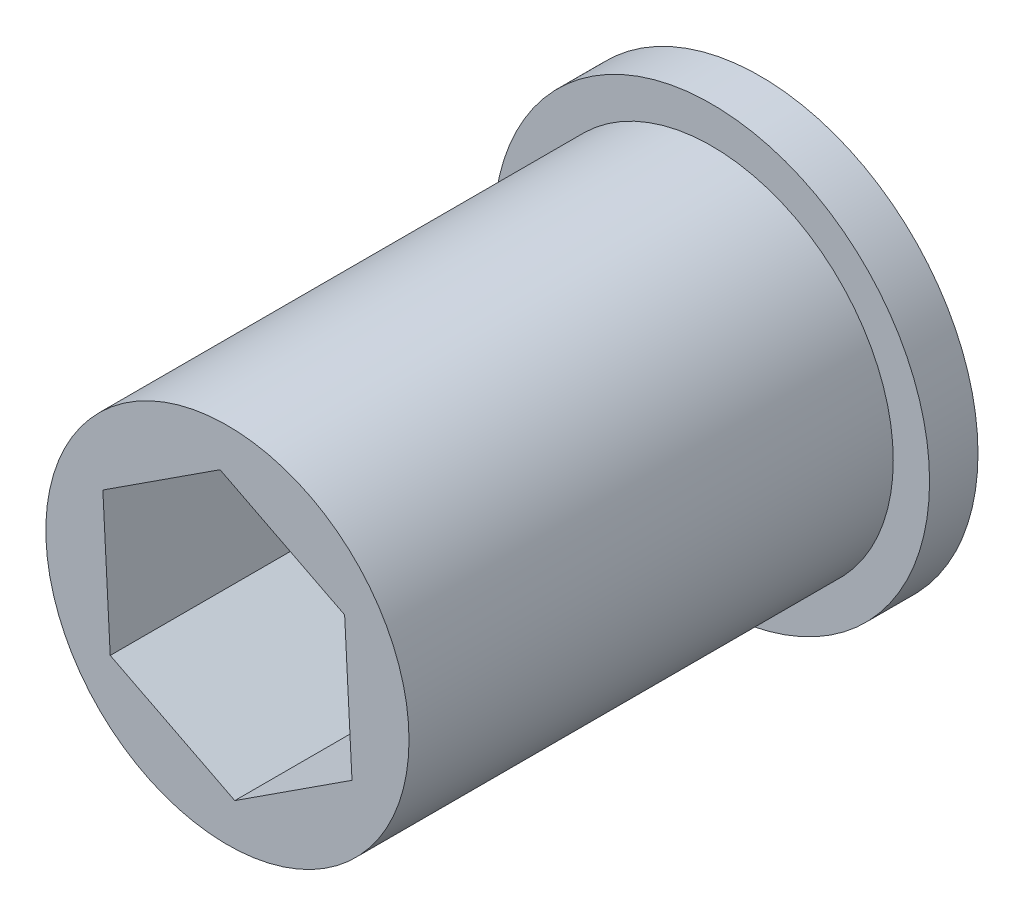
SolidWorks part; units mm, degrees
ref_plane "Front Plane" through (0, 0, 0) normal (0, 0, 1) x (1, 0, 0)
ref_plane "Top Plane" through (0, 0, 0) normal (0, 1, 0) x (1, 0, 0)
ref_plane "Right Plane" through (0, 0, 0) normal (1, 0, 0) x (0, 0, -1)
sketch "Sketch1" plane through (0, 0, 0) normal (0, 0, 1) x (1, 0, 0)
  line L1 (6.1478, 3.996) -> (-0.3868, 7.3221)
  line L2 (-0.3868, 7.3221) -> (-6.5346, 3.3261)
  line L3 (-6.5346, 3.3261) -> (-6.1478, -3.996)
  line L4 (-6.1478, -3.996) -> (0.3868, -7.3221)
  line L5 (0.3868, -7.3221) -> (6.5346, -3.3261)
  line L6 (6.5346, -3.3261) -> (6.1478, 3.996)
  circle A0 centre (0, 0) radius 11.43
  circle A1 centre (0, 0) radius 6.35 construction
  circle A2 centre (0, 0) radius 9.525
  dimension "D1" = 22.86
  dimension "D3" = 19.05
  dimension "D2" = 12.7
extrude "Boss-Extrude1" add sketch "Sketch1" along normal blind 27.94 contours A2 L6 L5 L4 L3 L2 L1 region at (-9.2556, 0, 0)
extrude "Boss-Extrude2" add sketch "Sketch1<5>" along normal blind 2.54 contours A0 A2 region at (-11.1067, 0, 0)
sketch "Sketch1<5>" plane through (0, 0, 0) normal (0, 0, 1) x (1, 0, 0) same geometry as "Sketch1"
